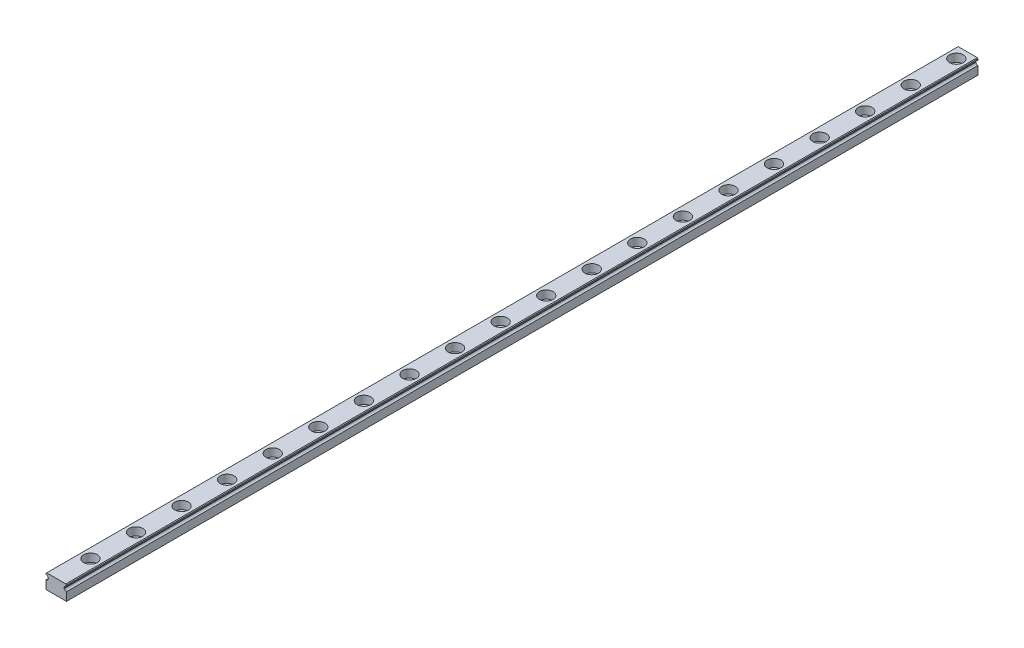
SolidWorks part; units mm, degrees
ref_plane "Спереди" through (0, 0, 0) normal (0, 0, 1) x (1, 0, 0)
ref_plane "Сверху" through (0, 0, 0) normal (0, 1, 0) x (1, 0, 0)
ref_plane "Справа" through (0, 0, 0) normal (1, 0, 0) x (0, 0, -1)
sketch "Sketch1" plane through (0, 0, 0) normal (0, 0, 1) x (1, 0, 0)
  line L0 (0, 0) -> (0, 5.7299) construction
  line L1 (-4.5, -3.25) -> (4.5, -3.25)
  line L2 (-4.5, -3.25) -> (-4.5, 0.45)
  line L3 (-4.5, 3.25) -> (4.5, 3.25)
  line L4 (4.5, -3.25) -> (4.5, 0.45)
  line L5 (-4.5, -3.25) -> (4.5, 3.25) construction
  line L6 (-4.5, 3.25) -> (4.5, -3.25) construction
  line L7 (-4.5, 2.45) -> (-4.5, 3.25)
  line L8 (-3.5318, 1.2) -> (-3.4, 1.2)
  line L9 (3.5318, 1.2) -> (3.4, 1.2)
  line L10 (-3.5318, 1.7) -> (-3.4, 1.7)
  line L11 (-3.4, 1.2) -> (-3.4, 1.7)
  line L12 (3.4, 1.2) -> (3.4, 1.7)
  line L13 (3.5318, 1.7) -> (3.4, 1.7)
  line L14 (4.5, 2.45) -> (4.5, 3.25)
  line L15 (-3.4, 1.45) -> (-4.5, 1.45) construction
  arc A0 (-3.5318, 1.7) -> (-4.5, 2.45) centre (-4.5, 1.45) ccw
  arc A1 (-4.5, 0.45) -> (-3.5318, 1.2) centre (-4.5, 1.45) ccw
  arc A2 (4.5, 0.45) -> (3.5318, 1.2) centre (4.5, 1.45) cw
  arc A3 (3.5318, 1.7) -> (4.5, 2.45) centre (4.5, 1.45) cw
  point P0 (0, 0)
  dimension "D3" = 1
  dimension "D1" = 9
  dimension "D2" = 6.5
  dimension "D4" = 2.05
  dimension "D5" = 6.8
  dimension "D6" = 0.5
extrude "Extrude1" add sketch "Sketch1" along normal blind 400
sketch "Sketch2" plane through (0, 3.25, 0) normal (0, 1, 0) x (1, 0, 0)
  line L0 (4.5, 0) -> (-4.5, 0) construction
  circle A0 centre (0, -5) radius 1.75
  circle A1 centre (0, -5) radius 3
  dimension "D1" = 3.5
  dimension "D2" = 6
  dimension "D3" = 5
extrude "Extrude2" cut sketch "Sketch2" against normal blind 3.5 contours A1
extrude "Extrude3" cut sketch "Sketch" against normal through all contours A0
sketch "Sketch" plane through (0, 3.25, 0) normal (0, 1, 0) x (1, 0, 0) same geometry as "Sketch2"
pattern_linear "LPattern1" count 40 spacing 20 along (0, 0, 1) of "Extrude2", "Extrude3"
chamfer "Chamfer1" distance 0.3 angle 45 2 edges at (4.5, 3.25, 200) (-4.5, 3.25, 200)
